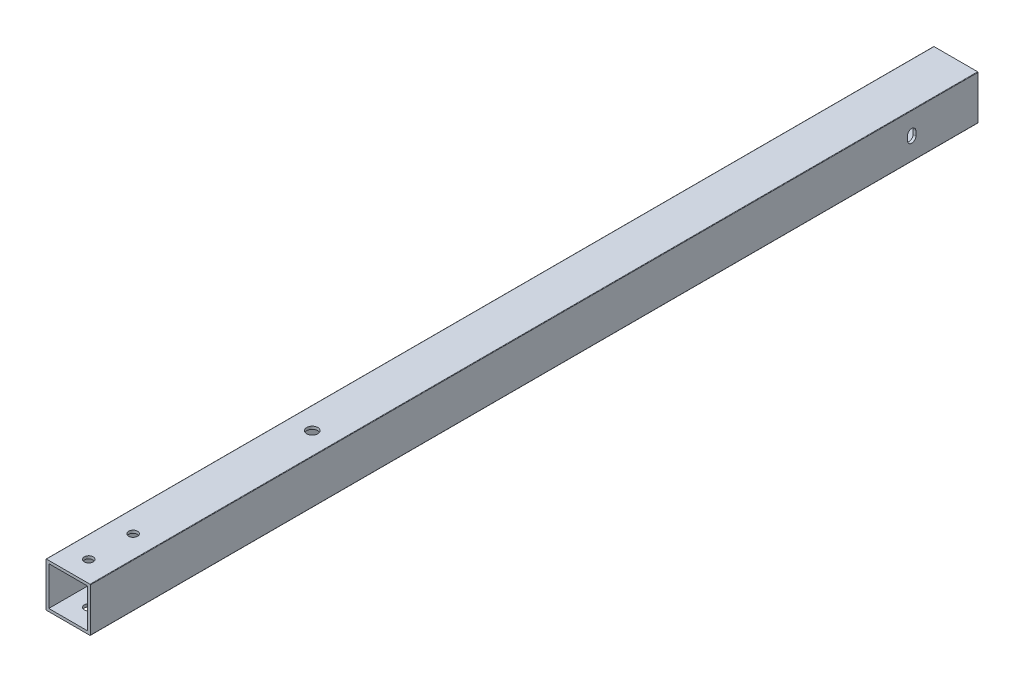
SolidWorks part; units mm, degrees
material "1060 Alloy"
ref_plane "Front Plane" through (0, 0, 0) normal (0, 0, 1) x (1, 0, 0)
ref_plane "Top Plane" through (0, 0, 0) normal (0, 1, 0) x (1, 0, 0)
ref_plane "Right Plane" through (0, 0, 0) normal (1, 0, 0) x (0, 0, -1)
ref_plane "Plane1" through (0, 0, 0) normal (0, 0, -1) x (-1, 0, 0)
sketch "Sketch1" plane through (0, 0, 0) normal (0, 0, -1) x (-1, 0, 0)
  line L4 (1.5875, -1.3335) -> (1.5875, 23.5585)
  line L5 (1.3335, 23.8125) -> (-23.5585, 23.8125)
  line L6 (-23.8125, 23.5585) -> (-23.8125, -1.3335)
  line L7 (-23.5585, -1.5875) -> (1.3335, -1.5875)
  line L9 (0, 22.225) -> (-22.225, 22.225)
  line L10 (0, 22.225) -> (0, 0)
  line L11 (0, 0) -> (-22.225, 0)
  line L12 (-22.225, 22.225) -> (-22.225, 0)
  line L13 (0, 22.225) -> (-22.225, 0) construction
  line L14 (0, 0) -> (-22.225, 22.225) construction
  arc A4 (1.3335, -1.5875) -> (1.5875, -1.3335) centre (1.3335, -1.3335) ccw
  arc A5 (1.5875, 23.5585) -> (1.3335, 23.8125) centre (1.3335, 23.5585) ccw
  arc A6 (-23.5585, 23.8125) -> (-23.8125, 23.5585) centre (-23.5585, 23.5585) ccw
  arc A7 (-23.8125, -1.3335) -> (-23.5585, -1.5875) centre (-23.5585, -1.3335) ccw
  point P24 (-11.1125, 11.1125)
  dimension "D1" = 25.4
  dimension "D2" = 25.4
  dimension "D3" = 1.5875
  dimension "D4" = 1.5875
  dimension "D5" = 1.5875
extrude "Boss-Extrude1" add sketch "Sketch1" against normal blind 508
sketch "Sketch2" plane through (-1.5875, 0, 0) normal (-1, 0, 0) x (0, 0, 1)
  line L0 (0, -1.3335) -> (0, 23.5585) construction
  line L1 (508, -1.3335) -> (0, -1.3335) construction
  line L2 (508, -1.3335) -> (508, 23.5585) construction
  circle A0 centre (12.6975, 11.3665) radius 1.5875
  circle A1 centre (495.3, 11.3665) radius 1.5875
  circle A2 centre (76.2, 11.3665) radius 6.35
  circle A3 centre (431.8, 11.3665) radius 6.35
  point P4 (0, 11.1125)
  dimension "D1" = 3.175
  dimension "D2" = 12.7
  dimension "D3" = 12.7
  dimension "D4" = 3.175
  dimension "D5" = 12.7
  dimension "D6" = 12.7
  dimension "D7" = 12.7
  dimension "D8" = 12.7
  dimension "D9" = 76.2
  dimension "D10" = 12.7
  dimension "D11" = 12.7
  dimension "D12" = 76.2
extrude "Cut-Extrude1" [suppressed] cut sketch "Sketch2" against normal through all
sketch "Sketch4" plane through (23.8125, 0, 0) normal (1, 0, 0) x (0, 0, -1)
  line L2 (-40.3145, 9.8425) -> (-40.3145, 12.3825)
  line L4 (-35.552, 9.8425) -> (-35.552, 12.3825)
  line L6 (-40.3145, 12.3825) -> (-35.552, 12.3825)
  line L7 (-40.3145, 11.1125) -> (-35.552, 11.1125)
  line L8 (0, 23.5585) -> (0, -1.3335) construction
  line L9 (0, 11.1125) -> (-49.6378, 11.1125)
  circle A0 centre (-37.9333, 9.8425) radius 2.3812
  circle A1 centre (-37.9333, 12.3825) radius 2.3812
  dimension "D1" = 4.7625
  dimension "D2" = 37.9333
  dimension "D3" = 1.27
extrude "Cut-Extrude2" cut sketch "Sketch4" against normal through all contours L6 A1 | L6 A1 A0 | L9 A0 | L9 A1 | A1 A0 | A0 L4 L7 | A1 L7 L4 | A0 L7 L2 | A1 L2 L7 | A0 region at (23.8125, 9.1445, 37.9333) region at (23.8125, 10.8001, 40.2061) region at (23.8125, 11.4249, 40.2061) region at (23.8125, 10.8001, 35.6605) region at (23.8125, 11.5673, 37.9333) region at (23.8125, 11.7352, 40.1736) region at (23.8125, 10.6577, 37.9333) region at (23.8125, 13.3931, 37.9333) region at (23.8125, 11.4249, 35.6605)
sketch "Sketch6" plane through (0, -1.5875, 0) normal (0, -1, 0) x (1, 0, 0)
  line L0 (11.1125, 508) -> (11.1125, 368.3) construction
  line L1 (23.5585, 508) -> (-1.3335, 508) construction
  circle A0 centre (11.1125, 368.3) radius 3.175
  dimension "D2" = 6.35
  dimension "D1" = 139.7
extrude "Cut-Extrude4" cut sketch "Sketch6" against normal through all
sketch "Sketch7" plane through (0, -1.5875, 0) normal (0, -1, 0) x (1, 0, 0)
  circle A0 centre (10.9125, 470.65) radius 2.54
  circle A1 centre (10.9125, 496.05) radius 2.54
extrude "Cut-Extrude5" cut sketch "Sketch7" against normal through all
